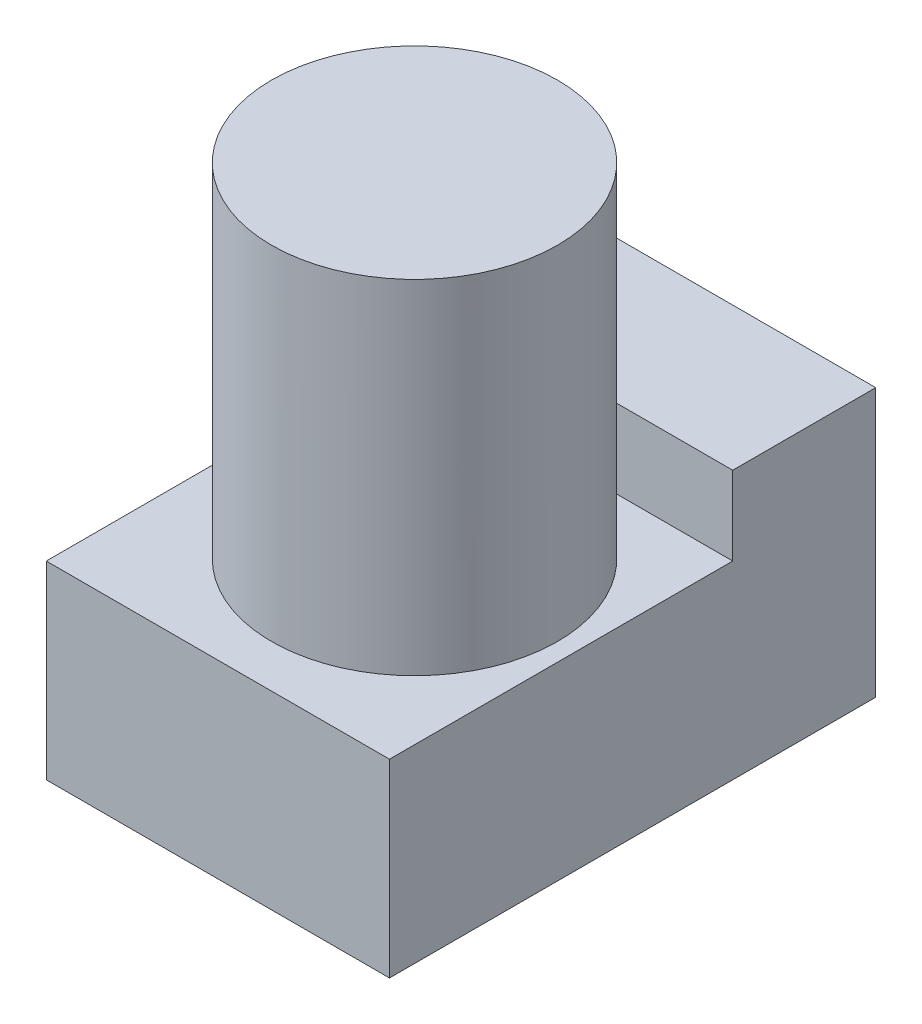
SolidWorks part; units mm, degrees
ref_plane "Plan de face" through (0, 0, 0) normal (0, 0, 1) x (1, 0, 0)
ref_plane "Plan de dessus" through (0, 0, 0) normal (0, 1, 0) x (1, 0, 0)
ref_plane "Plan de droite" through (0, 0, 0) normal (1, 0, 0) x (0, 0, -1)
sketch "Sketch1" plane through (0, 0, 0) normal (1, 0, 0) x (0, 0, -1)
  line L0 (-152.7943, -56.4036) -> (126.5507, -56.4036) construction
  line L1 (-101.4493, 123.5964) -> (-101.4493, -121.4036) construction
  line L2 (-101.4493, -56.4036) -> (34.5507, -56.4036)
  line L3 (-101.4493, -56.4036) -> (-101.4493, -3.4036)
  line L4 (-101.4493, -3.4036) -> (-5.4493, -3.4036)
  line L5 (34.5507, -56.4036) -> (34.5507, -3.4036)
  line L6 (34.5507, -3.4036) -> (34.5507, 18.5964)
  line L7 (34.5507, 18.5964) -> (-5.4493, 18.5964)
  line L8 (-5.4493, -3.4036) -> (-5.4493, 18.5964)
  dimension "D1" = 136
  dimension "D2" = 53
  dimension "D3" = 22
  dimension "D4" = 40
extrude "Boss-Extrude1" add sketch "Sketch1" along normal blind 96
sketch "Sketch2" plane through (0, -3.4036, 0) normal (0, 1, 0) x (1, 0, 0)
  line L0 (0, -49.4493) -> (96, -49.4493) construction
  circle A0 centre (51, -49.4493) radius 40
  dimension "D2" = 80
  dimension "D1" = 52
  dimension "D3" = 45
extrude "Boss-Extrude2" add sketch "Sketch2" along normal blind 96 contours A0
